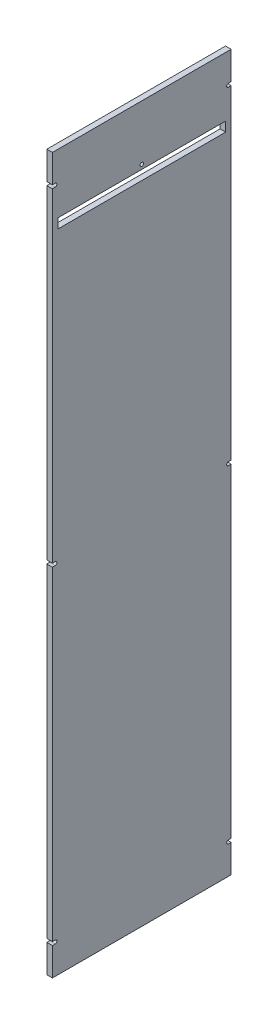
SolidWorks part; units mm, degrees
ref_plane "Front Plane" through (0, 0, 0) normal (0, 0, 1) x (1, 0, 0)
ref_plane "Top Plane" through (0, 0, 0) normal (0, 1, 0) x (1, 0, 0)
ref_plane "Right Plane" through (0, 0, 0) normal (1, 0, 0) x (0, 0, -1)
sketch "Sketch1" plane through (0, 0, 0) normal (0, 1, 0) x (1, 0, 0)
  line L1 (0, 0) -> (4.7625, 0)
  line L2 (0, 0) -> (0, 152.4)
  line L3 (0, 152.4) -> (4.7625, 152.4)
  line L4 (4.7625, 0) -> (4.7625, 152.4)
  dimension "D1" = 152.4
  dimension "D2" = 4.7625
extrude "Boss-Extrude1" add sketch "Sketch1" along normal blind 609.6
sketch "Sketch2" plane through (4.7625, 0, 0) normal (1, 0, 0) x (0, 0, -1)
  line L1 (147.6375, 558.8) -> (4.7625, 558.8)
  line L2 (147.6375, 558.8) -> (147.6375, 550.8625)
  line L3 (147.6375, 550.8625) -> (4.7625, 550.8625)
  line L4 (4.7625, 558.8) -> (4.7625, 550.8625)
extrude "Cut-Extrude1" cut sketch "Sketch2" against normal through all
sketch "Sketch3" plane through (0, 0, 0) normal (-1, 0, 0) x (0, 0, 1)
  line L0 (-2.3813, 0) -> (-2.3813, 23.9395) construction
  line L1 (-152.4, 0) -> (0, 0) construction
  line L2 (-152.4, 609.6) -> (0, 609.6) construction
  line L3 (-150.0188, 0) -> (-150.0188, 23.9395) construction
  line L4 (0, 609.6) -> (0, 0) construction
  line L5 (-152.4, 609.6) -> (-152.4, 0) construction
  line L6 (0, 584.2) -> (-152.4, 584.2) construction
  line L7 (0, 25.4) -> (-152.4, 25.4) construction
  line L8 (0, 304.8) -> (-152.4, 304.8) construction
  line L9 (-2.3813, 582.7395) -> (0, 582.7395)
  line L10 (-2.3813, 585.6605) -> (0, 585.6605)
  line L11 (-150.0188, 585.6605) -> (-152.4, 585.6605)
  line L12 (-150.0188, 582.7395) -> (-152.4, 582.7395)
  line L13 (-150.0188, 303.3395) -> (-152.4, 303.3395)
  line L14 (-150.0188, 306.2605) -> (-152.4, 306.2605)
  line L15 (-2.3813, 303.3395) -> (0, 303.3395)
  line L16 (-2.3813, 306.2605) -> (0, 306.2605)
  line L17 (-152.4, 303.3395) -> (-152.4, 306.2605)
  line L18 (-2.3813, 23.9395) -> (0, 23.9395)
  line L20 (-2.3813, 26.8605) -> (0, 26.8605)
  line L21 (0, 23.9395) -> (0, 26.8605)
  line L22 (-150.0188, 23.9395) -> (-152.4, 23.9395)
  line L23 (-2.3813, 26.8605) -> (-2.3813, 609.6) construction
  line L24 (-150.0188, 26.8605) -> (-152.4, 26.8605)
  line L25 (-152.4, 23.9395) -> (-152.4, 26.8605)
  line L26 (-152.4, 582.7395) -> (-152.4, 585.6605)
  line L27 (0, 582.7395) -> (0, 585.6605)
  line L28 (0, 303.3395) -> (0, 306.2605)
  line L30 (-150.0188, 26.8605) -> (-150.0188, 609.6) construction
  arc A0 (-2.3813, 26.8605) -> (-2.3813, 23.9395) centre (-2.3813, 25.4) ccw
  arc A1 (-150.0188, 23.9395) -> (-150.0188, 26.8605) centre (-150.0188, 25.4) ccw
  arc A2 (-150.0188, 303.3395) -> (-150.0188, 306.2605) centre (-150.0188, 304.8) ccw
  arc A3 (-150.0188, 582.7395) -> (-150.0188, 585.6605) centre (-150.0188, 584.2) ccw
  arc A4 (-2.3813, 585.6605) -> (-2.3813, 582.7395) centre (-2.3813, 584.2) ccw
  arc A5 (-2.3813, 306.2605) -> (-2.3813, 303.3395) centre (-2.3813, 304.8) ccw
  dimension "D5" = 2.921
  dimension "D1" = 2.3813
  dimension "D2" = 2.3813
  dimension "D3" = 25.4
  dimension "D4" = 25.4
extrude "Cut-Extrude2" cut sketch "Sketch3" against normal through all
hole_wizard "#4 Clearance Hole1" positions "Sketch4" profile "Sketch5" hole size "#4" standard "ANSI Inch" end condition through all
sketch "Sketch4" plane through (0, 0, 0) normal (-1, 0, 0) x (0, 0, 1)
  line L0 (0, 562.7688) -> (-152.4, 562.7688) construction
  line L1 (0, 582.7395) -> (0, 306.2605) construction
  line L2 (-152.4, 582.7395) -> (-152.4, 306.2605) construction
  line L4 (-147.6375, 558.8) -> (-4.7625, 558.8) construction
  point P11 (-76.2, 562.7688)
  dimension "D1" = 3.9688
sketch "Sketch5" plane through (0, 562.7688, -76.2) normal (0, 1, 0) x (0, 0, 1)
  line L0 (0, 0) -> (0, 4.7625)
  line L1 (0, 4.7625) -> (1.4732, 4.7625)
  line L2 (1.4732, 4.7625) -> (1.4732, 0)
  line L5 (1.4732, 0) -> (0, 0)
  line L11 (0, -6.35) -> (0, 107.95) construction
  dimension "Thru Hole Dia." = 2.9464
  dimension "Thru Hole Depth" = 4.7625
sketch "Sketch6" plane through (0, 0, 0) normal (-1, 0, 0) x (0, 0, 1)
  line L0 (-147.6375, 550.8625) -> (-147.6375, 558.8) construction
  line L1 (-147.6375, 558.8) -> (-4.7625, 558.8) construction
  line L2 (-4.7625, 558.8) -> (-4.7625, 550.8625) construction
  line L3 (-4.7625, 550.8625) -> (-147.6375, 550.8625) construction
  line L4 (-147.6375, 550.8625) -> (-147.6375, 558.8)
  line L5 (-147.6375, 558.8) -> (-4.7625, 558.8)
  line L6 (-4.7625, 558.8) -> (-4.7625, 550.8625)
  line L7 (-4.7625, 550.8625) -> (-147.6375, 550.8625)
  line L8 (-147.7645, 550.7355) -> (-147.7645, 558.927)
  line L9 (-147.7645, 558.927) -> (-4.6355, 558.927)
  line L10 (-4.6355, 558.927) -> (-4.6355, 550.7355)
  line L11 (-4.6355, 550.7355) -> (-147.7645, 550.7355)
  dimension "D1" = 0.127
extrude "Cut-Extrude3" cut sketch "Sketch6" against normal through all
